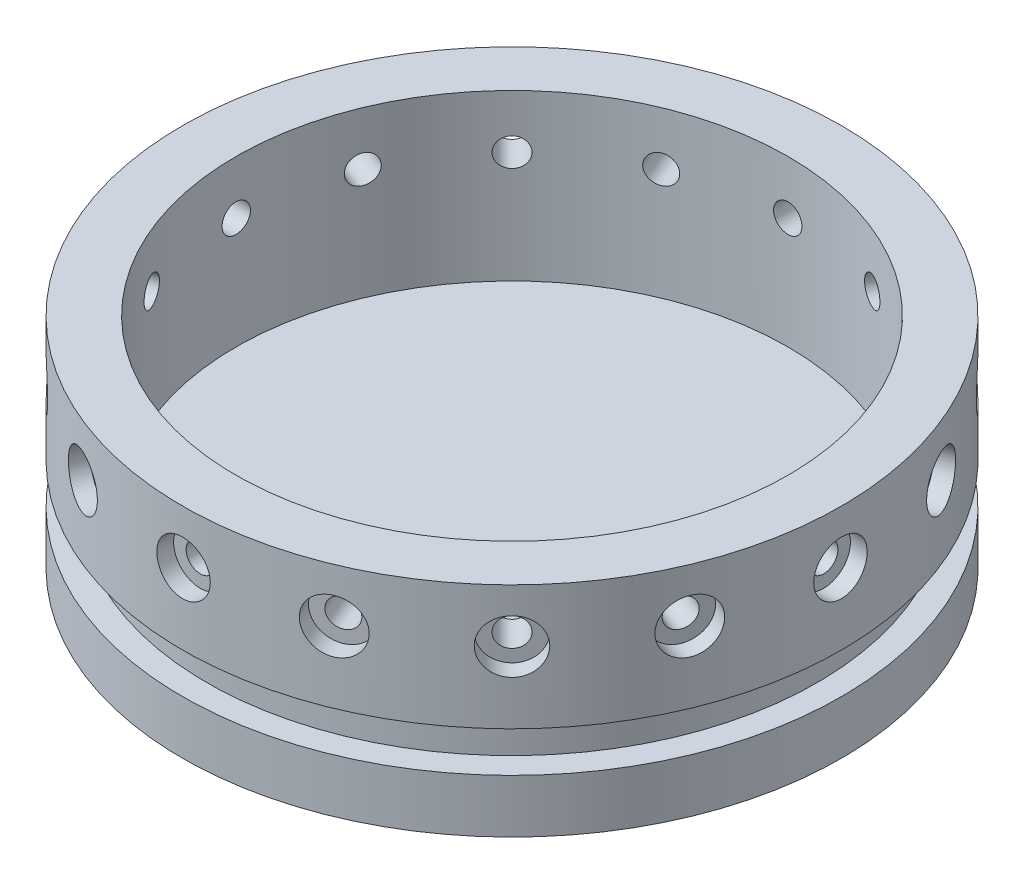
SolidWorks part; units mm, degrees
material "6061-T6 (SS)"
ref_plane "Front Plane" through (0, 0, 0) normal (0, 0, 1) x (1, 0, 0)
ref_plane "Top Plane" through (0, 0, 0) normal (0, 1, 0) x (1, 0, 0)
ref_plane "Right Plane" through (0, 0, 0) normal (1, 0, 0) x (0, 0, -1)
sketch "Sketch1" plane through (0, 0, 0) normal (0, 0, 1) x (1, 0, 0)
  line L1 (0, 0) -> (58.7375, 0)
  line L2 (58.7375, 0) -> (58.7375, 50.8) construction
  line L3 (0, 38.9382) -> (9.525, 38.9382)
  line L4 (58.7375, 0) -> (58.7375, 9.525)
  line L5 (58.7375, 9.525) -> (9.525, 9.525)
  line L6 (9.525, 9.525) -> (9.525, 38.9382)
  line L7 (0, 16.7132) -> (0, 26.2382)
  line L8 (0, 0) -> (0, 9.525)
  line L9 (0, 9.525) -> (4.318, 9.525)
  line L10 (4.318, 9.525) -> (4.318, 16.7132)
  line L11 (4.318, 16.7132) -> (0, 16.7132)
  line L13 (0, 26.2382) -> (0, 32.5882)
  line L14 (0, 32.5882) -> (0, 38.9382)
  dimension "D2" = 58.7375
  dimension "D3" = 9.525
  dimension "D4" = 9.525
  dimension "D5" = 7.1882
  dimension "D6" = 4.318
  dimension "D7" = 9.525
  dimension "D8" = 6.35
  dimension "D9" = 6.35
revolve "Revolve1" add sketch "Sketch1" angle 360 about L2 region at (0.7047, 4.7625, 0)
ref_plane "Plane1" through (0, 0, -58.7375) normal (0, 0, -1) x (-1, 0, 0)
sketch "Sketch12" plane through (0, 0, -58.7375) normal (0, 0, -1) x (-1, 0, 0)
  line L0 (-58.7375, 38.9382) -> (-58.7375, 29.4132)
  line L1 (-9.525, 38.9382) -> (-107.95, 38.9382) construction
  point P5 (-58.7375, 29.4132)
hole_wizard "CBORE for 1/4 Socket Head Cap Screw1" positions "Sketch14" profile "Sketch15" counterbore size "1/4" standard "ANSI Inch" end condition through all
sketch "Sketch14" plane through (0, 0, -58.7375) normal (0, 0, -1) x (-1, 0, 0)
  point P0 (-58.7375, 29.4132)
sketch "Sketch15" plane through (58.7375, 29.4132, -58.7375) normal (1, 0, 0) x (0, 1, 0)
  line L0 (0, 0) -> (0, 117.475)
  line L1 (0, 117.475) -> (2.5273, 117.475)
  line L3 (2.5273, 117.475) -> (2.5273, 3.175)
  line L4 (2.5273, 3.175) -> (4.7625, 3.175)
  line L5 (4.7625, 3.175) -> (4.7625, 0)
  line L7 (4.7625, 0) -> (0, 0)
  line L11 (0, -6.35) -> (0, 107.95) construction
  dimension "Thru Hole Dia." = 5.0546
  dimension "Thru Hole Depth" = 117.475
  dimension "C'Bore Dia." = 9.525
  dimension "C'Bore Depth" = 3.175
sketch "Sketch16" plane through (0, 0, 0) normal (0, 0, 1) x (1, 0, 0)
  line L0 (58.7375, 0) -> (58.7375, 38.9382) construction
  line L1 (0, 0) -> (117.475, 0) construction
pattern_circular "CirPattern1" count 16 over 360 about axis through (58.7375, 0, 0) along (0, 1, 0) of "CBORE for 1/4 Socket Head Cap Screw1"
ref_plane "Plane2" through (0, 29.4132, 0) normal (0, 1, 0) x (1, 0, 0)
